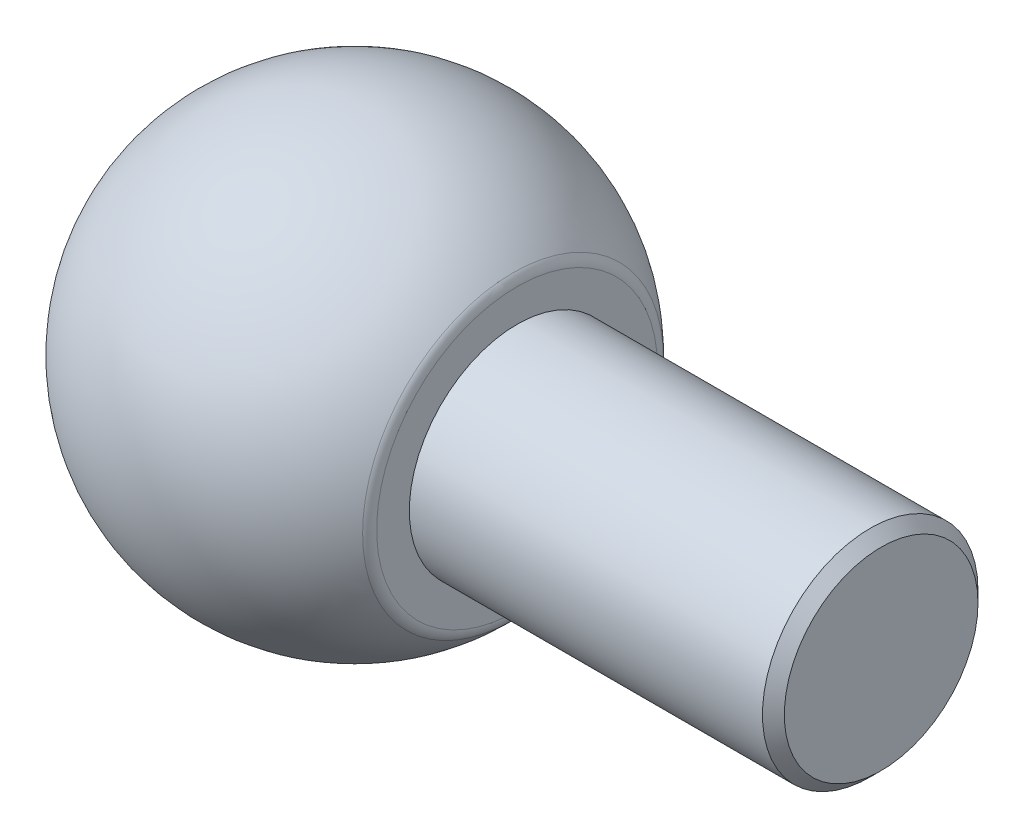
SolidWorks part; units mm, degrees
ref_plane "前视基准面" through (0, 0, 0) normal (0, 0, 1) x (1, 0, 0)
ref_plane "上视基准面" through (0, 0, 0) normal (0, 1, 0) x (1, 0, 0)
ref_plane "右视基准面" through (0, 0, 0) normal (1, 0, 0) x (0, 0, -1)
sketch "草图1" plane through (0, 0, 0) normal (0, 0, 1) x (1, 0, 0)
  line L0 (0, 3) -> (0, -3)
  arc A0 (0, -3) -> (0, 3) centre (0, 0) ccw
revolve "旋转1" add sketch "草图1" angle 360 about L0
ref_plane "基准面1" through (10, 0, 0) normal (1, 0, 0) x (0, 0, -1)
sketch "草图2" plane through (10, 0, 0) normal (1, 0, 0) x (0, 0, -1)
  circle A0 centre (0, 0) radius 2
extrude "切除-拉伸1" cut sketch "草图2" against normal blind 7.77
ref_plane "基准面2" through (2.23, 0, 0) normal (1, 0, 0) x (0, 0, -1)
sketch "草图3" plane through (2.23, 0, 0) normal (1, 0, 0) x (0, 0, -1)
  circle A0 centre (0, 0) radius 1.48
extrude "凸台-拉伸1" add sketch "草图3" along normal blind 5
cosmetic thread "装饰螺纹线1" parameters "D2"=2.013
fillet "圆角2" radius 0.2 1 edges at (2.2361, 0, 2)
fillet "圆角3" radius 0.2 1 edges at (2.23, 0, -2)
chamfer "倒角1" distance 0.15 angle 45 1 edges at (7.23, 0, -1.48)
ref_plane "基准面3" through (0, -5, 0) normal (0, 1, 0) x (-1, 0, 0)
sketch "草图4" plane through (0, -5, 0) normal (0, 1, 0) x (-1, 0, 0)
  circle A0 centre (0, 0) radius 1.6
extrude "切除-拉伸3" cut sketch "草图4" along normal blind 2.465
hole_wizard "M3 螺纹孔2" positions "3D草图2" profile "草图6" tap size "M3" standard "GB"
sketch3d "3D草图2"
  line L0 (0, -2.535, 0) -> (0, -2.5377, 0) construction
  point P0 (0, -2.535, 0)
sketch "草图6" plane through (0, -2.535, 0) normal (1, 0, 0) x (0, 0, -1)
  line L0 (0, 0) -> (0, 4.7511)
  line L1 (0, 4.7511) -> (1.25, 4)
  line L2 (1.25, 4) -> (1.25, 0)
  line L5 (1.25, 0) -> (0, 0)
  line L10 (0, 4.7511) -> (-1.25, 4) construction
  line L11 (0, -6.35) -> (0, 107.95) construction
  dimension "螺纹孔钻头直径" = 2.5
  dimension "螺纹孔钻头深度" = 4
  dimension "导头角度" = 118
cosmetic thread "孔螺蚊线2" parameters "D1"=3, "D2"=3
